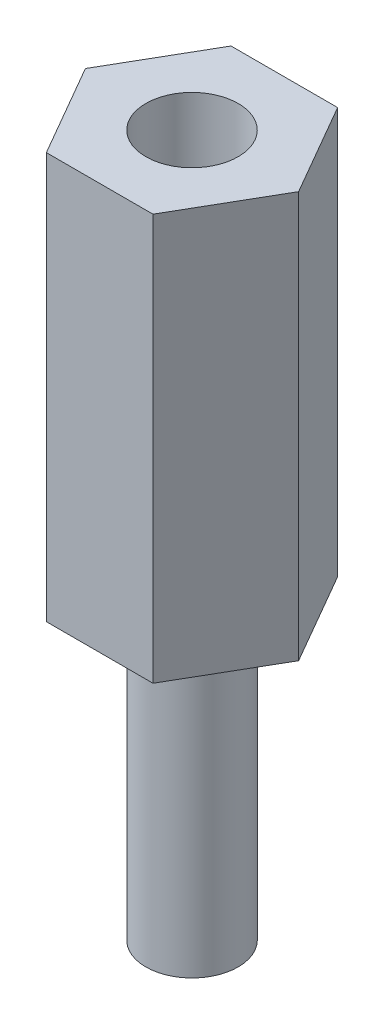
SolidWorks part; units mm, degrees
ref_plane "Front Plane" through (0, 0, 0) normal (0, 0, 1) x (1, 0, 0)
ref_plane "Top Plane" through (0, 0, 0) normal (0, 1, 0) x (1, 0, 0)
ref_plane "Right Plane" through (0, 0, 0) normal (1, 0, 0) x (0, 0, -1)
sketch "Sketch1" plane through (0, 0, 0) normal (0, 1, 0) x (1, 0, 0)
  line L1 (-2.8868, 0) -> (-1.4434, -2.5)
  line L2 (-1.4434, -2.5) -> (1.4434, -2.5)
  line L3 (1.4434, -2.5) -> (2.8868, 0)
  line L4 (2.8868, 0) -> (1.4434, 2.5)
  line L5 (1.4434, 2.5) -> (-1.4434, 2.5)
  line L6 (-1.4434, 2.5) -> (-2.8868, 0)
  circle A0 centre (0, 0) radius 1.25
  circle A1 centre (0, 0) radius 2.5 construction
  dimension "D2" = 2.5
  dimension "D1" = 5
extrude "Boss-Extrude1" add sketch "Sketch1" along normal blind 11
extrude "Boss-Extrude2" add sketch "Sketch1<2>" against normal blind 8 and the other way blind 2 contours A0 region at (0, 0, 0)
sketch "Sketch1<2>" plane through (0, 0, 0) normal (0, 1, 0) x (1, 0, 0) same geometry as "Sketch1"
